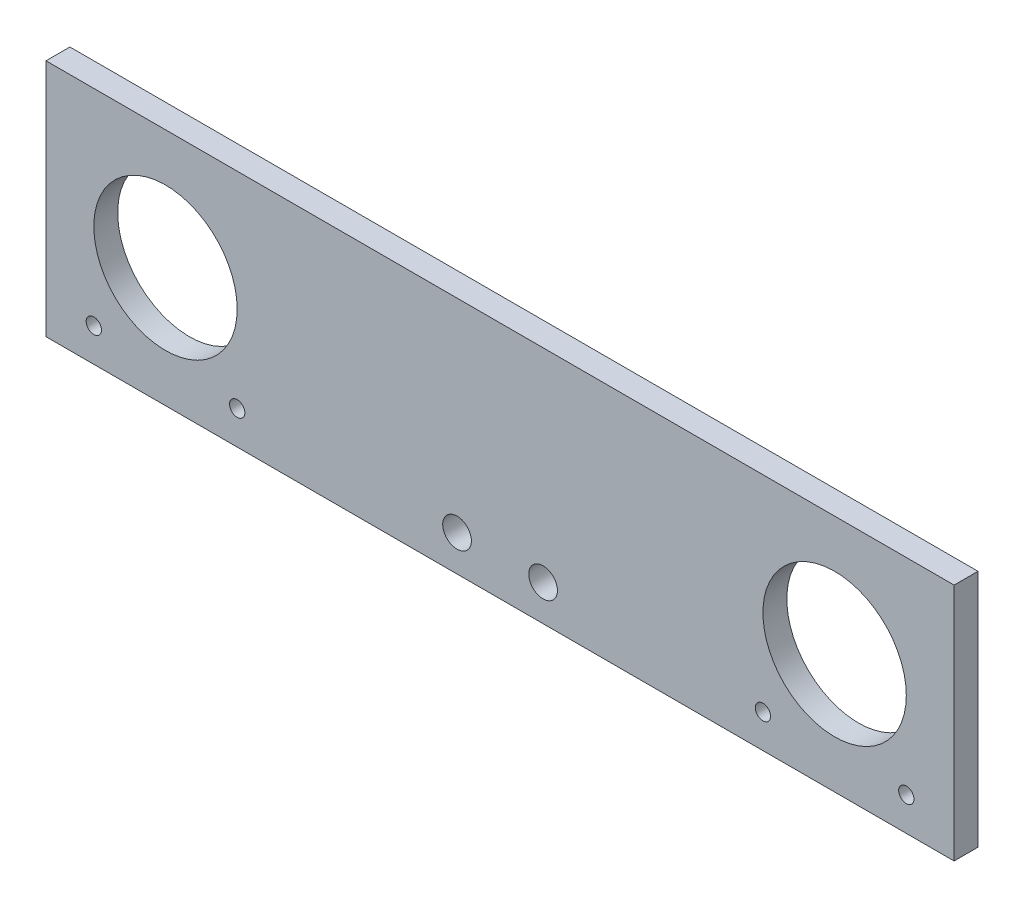
SolidWorks part; units mm, degrees
ref_plane "Front Plane" through (0, 0, 0) normal (0, 0, 1) x (1, 0, 0)
ref_plane "Top Plane" through (0, 0, 0) normal (0, 1, 0) x (1, 0, 0)
ref_plane "Right Plane" through (0, 0, 0) normal (1, 0, 0) x (0, 0, -1)
sketch "Sketch1" plane through (0, 0, 0) normal (0, 0, 1) x (1, 0, 0)
  line L1 (0, 0) -> (190, 0)
  line L2 (0, 0) -> (0, 50)
  line L3 (0, 50) -> (190, 50)
  line L4 (190, 0) -> (190, 50)
  circle A0 centre (25, 25) radius 15
  circle A1 centre (165, 25) radius 15
  circle A2 centre (40, 7) radius 1.6
  circle A3 centre (180, 7) radius 1.6
  circle A4 centre (150, 7) radius 1.6
  circle A5 centre (10, 7) radius 1.6
  circle A6 centre (86, 7.5) radius 3
  circle A7 centre (104, 7.5) radius 3
  point P5 (95, 25)
  dimension "D3" = 30
  dimension "D7" = 30
  dimension "D9" = 3.2
  dimension "D11" = 15
  dimension "D15" = 3.2
  dimension "D16" = 7
  dimension "D23" = 6
  dimension "D24" = 6
  dimension "D12" = 7
  dimension "D14" = 3.2
  dimension "D18" = 3.2
  dimension "D2" = 50
  dimension "D4" = 70
  dimension "D5" = 95
  dimension "D6" = 25
  dimension "D8" = 70
  dimension "D10" = 15
  dimension "D13" = 7
  dimension "D17" = 15
  dimension "D20" = 7
  dimension "D21" = 25
  dimension "D22" = 25
  dimension "D25" = 7.5
  dimension "D26" = 7.5
  dimension "D27" = 9
  dimension "D32" = 95
  dimension "D35" = 9
extrude "Boss-Extrude1" add sketch "Sketch1" along normal blind 5 contours L3 L2 L1 A2 A0 | L1 L4 L3 A4 A1 region at (95, 25.1961, 0)
sketch "Sketch3" plane through (0, 0, 5) normal (0, 0, 1) x (1, 0, 0)
  circle A0 centre (10, 7) radius 2.75
  circle A1 centre (40, 7) radius 2.75
  circle A2 centre (150, 7) radius 2.75
  circle A3 centre (180, 7) radius 2.75
  dimension "D1" = 5.5
extrude "Cut-Extrude1" [suppressed] cut sketch "Sketch3" against normal blind 1.5 contours A0 | A1 | A2 | A3
